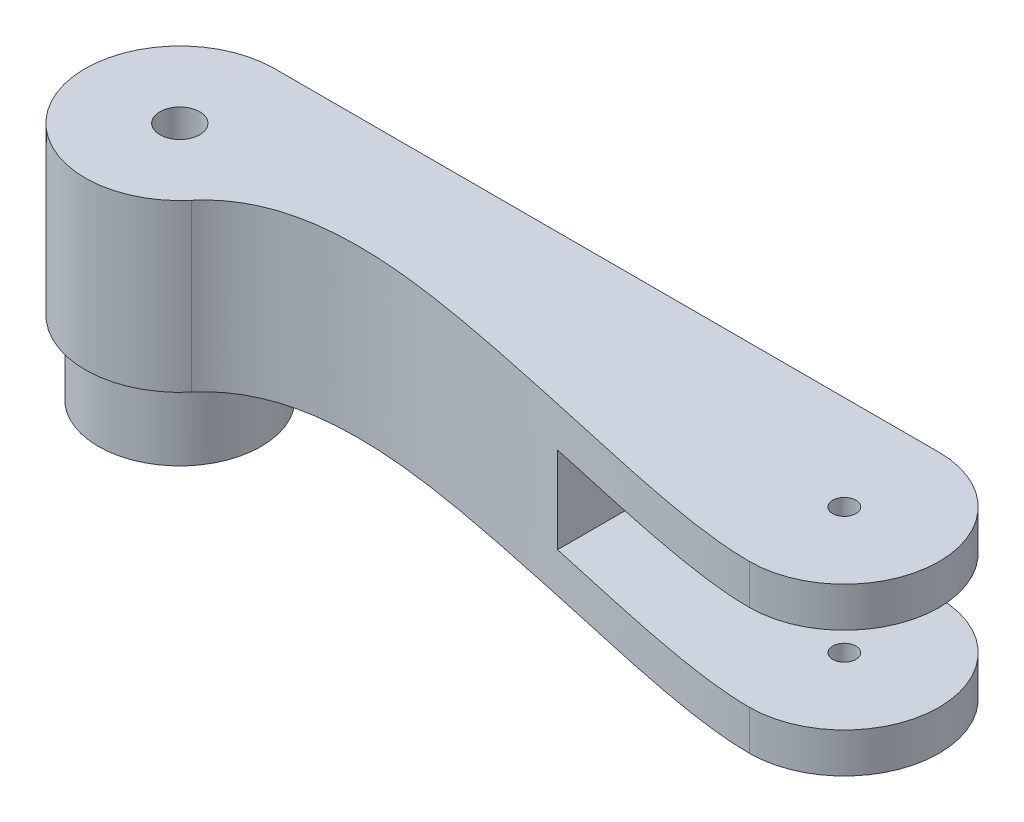
SolidWorks part; units mm, degrees
ref_plane "Front Plane" through (0, 0, 0) normal (0, 0, 1) x (1, 0, 0)
ref_plane "Top Plane" through (0, 0, 0) normal (0, 1, 0) x (1, 0, 0)
ref_plane "Right Plane" through (0, 0, 0) normal (1, 0, 0) x (0, 0, -1)
sketch "Sketch1" plane through (0, 0, 0) normal (0, 1, 0) x (1, 0, 0)
  line L0 (-50, 0) -> (50, 0) construction
  line L1 (-50, 14.25) -> (50, 14.25)
  line L2 (-50, -14.25) -> (50, -14.25)
  arc A0 (-50, 14.25) -> (-50, -14.25) centre (-50, 0) ccw
  arc A1 (50, -14.25) -> (50, 14.25) centre (50, 0) ccw
  point P3 (0, 0)
  dimension "D1" = 14.25
  dimension "D2" = 100
extrude "Boss-Extrude1" add sketch "Sketch1" along normal blind 6
sketch "Sketch3" plane through (0, 0, 0) normal (0, -1, 0) x (1, 0, 0)
  circle A0 centre (50, 0) radius 1.75
  dimension "D1" = 3.5
extrude "Cut-Extrude2" cut sketch "Sketch3" against normal through all
sketch "Sketch4" plane through (0, 6, 0) normal (0, 1, 0) x (1, 0, 0)
  line L0 (-50, 14.25) -> (15, 14.25)
  line L1 (-50, 14.25) -> (50, 14.25) construction
  line L2 (15, 14.25) -> (15, -14.25)
  line L3 (-50, -14.25) -> (50, -14.25) construction
  line L4 (15, -14.25) -> (-50, -14.25)
  arc A0 (-50, 14.25) -> (-50, -14.25) centre (-50, 0) ccw
  arc A1 (-50, 14.25) -> (-50, -14.25) centre (-50, 0) ccw construction
  dimension "D1" = 65
extrude "Boss-Extrude2" add sketch "Sketch4" along normal blind 13
sketch "Sketch5" plane through (0, 19, 0) normal (0, 1, 0) x (1, 0, 0)
  line L0 (-50, 0) -> (50, 0) construction
  line L1 (-50, 14.25) -> (50, 14.25)
  line L2 (-50, -14.25) -> (50, -14.25)
  arc A0 (-50, 14.25) -> (-50, -14.25) centre (-50, 0) ccw
  arc A1 (50, -14.25) -> (50, 14.25) centre (50, 0) ccw
  point P4 (0, 0)
  dimension "D1" = 14.25
extrude "Boss-Extrude3" add sketch "Sketch5" along normal blind 6
sketch "Sketch6" plane through (0, 25, 0) normal (0, 1, 0) x (1, 0, 0)
  circle A0 centre (50, 0) radius 1.75
  dimension "D1" = 3.5
extrude "Cut-Extrude3" cut sketch "Sketch6" against normal up to next
sketch "Sketch7" plane through (0, 25, 0) normal (0, 1, 0) x (1, 0, 0)
  line L0 (0, -15.6753) -> (0, 15.6753) construction
  line L1 (-50, -14.25) -> (50, -14.25)
  circle A0 centre (-50, 0) radius 14.25
  circle A1 centre (50, 0) radius 14.25
  spline S0 degree 3 poles (-39.0732, -9.1469) (-31.5141, -0.117) (5.4387, -4.6452) (38.6975, -14.25) (50, -14.25) knots 0 0 0 0 0.435908 1 1 1 1
  line M5 (-50, -14.25) -> (50, -14.25)
extrude "Cut-Extrude4" cut sketch "Sketch7" against normal up to next contours S0 A0 M5 region at (-8.5907, 25, 9.7914)
sketch "Sketch8" plane through (0, 0, 0) normal (0, -1, 0) x (1, 0, 0)
  circle A1 centre (-50, 0) radius 12.25
  dimension "D1" = 24.5
extrude "Boss-Extrude4" add sketch "Sketch8" along normal blind 11
sketch "Sketch9" plane through (0, -11, 0) normal (0, -1, 0) x (1, 0, 0)
  circle A0 centre (-50, 0) radius 6.75 construction
  circle A1 centre (-50, 6.75) radius 2.55
  circle A2 centre (-50, -6.75) radius 2.55
  arc A3 (-50, 14.25) -> (-50, -14.25) centre (-50, 0) ccw construction
  point P6 (-50, 0)
  dimension "D1" = 13.5
  dimension "D2" = 5.1
extrude "Cut-Extrude5" cut sketch "Sketch9" against normal blind 6
sketch "Sketch11" plane through (0, -11, 0) normal (0, -1, 0) x (1, 0, 0)
  circle A0 centre (-50, 0) radius 3
  dimension "D1" = 6
extrude "Cut-Extrude6" cut sketch "Sketch11" against normal through all both and the other way through all
equation "\"Length\"= 100mm"
equation "\"Radius\"= 14.25mm"
equation "\"Thick\"= 12mm"
equation "\"D1@Sketch1\"= \"Radius\""
equation "\"D2@Sketch1\" = \"Length\""
equation "\"D1@Boss-Extrude1\"= \"Thick\""
equation "\"D1@Sketch4\"=\"Length\"*0.65"
equation "\"D1@Sketch5\"=\"Radius\""
equation "\"D1@Boss-Extrude4\"=\"Thick\"-1"
